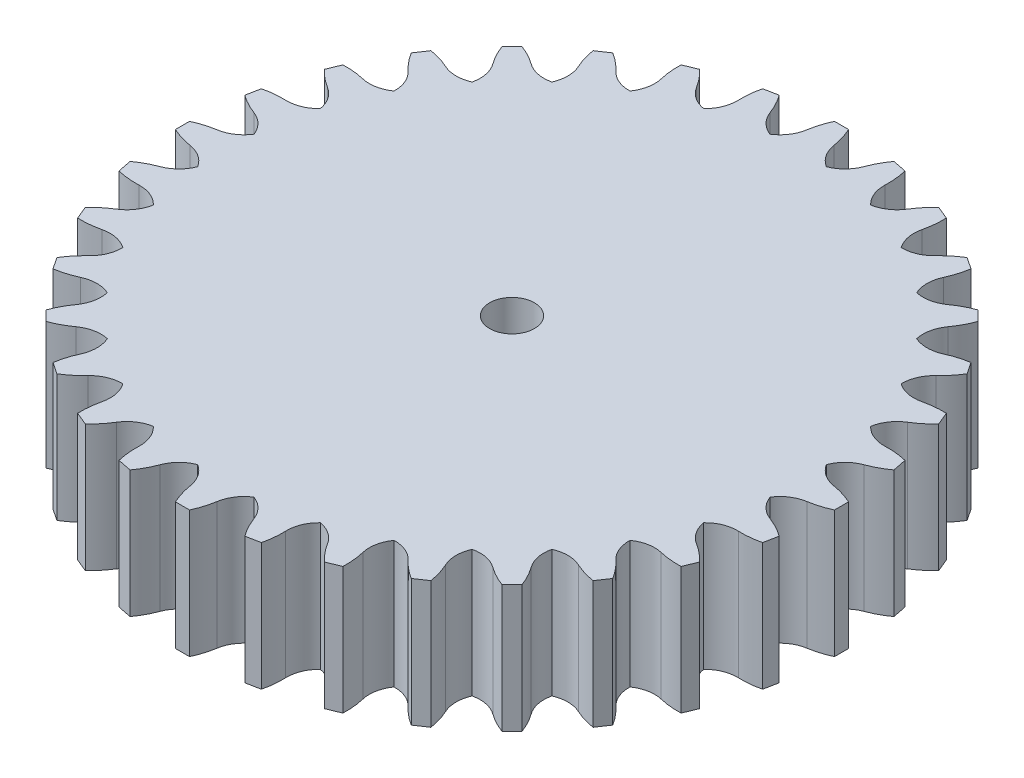
SolidWorks part; units mm, degrees
ref_plane "Front Plane" through (0, 0, 0) normal (0, 0, 1) x (1, 0, 0)
ref_plane "Top Plane" through (0, 0, 0) normal (0, 1, 0) x (1, 0, 0)
ref_plane "Right Plane" through (0, 0, 0) normal (1, 0, 0) x (0, 0, -1)
sketch "Sketch1" plane through (0, 0, 0) normal (0, 1, 0) x (1, 0, 0)
  line L2 (0.5, 23.3473) -> (-0.5, 23.3473)
  line L3 (-1, 20.3473) -> (1, 20.3473)
  line L4 (0, 23.3473) -> (0, 20.3473)
  line L6 (0, -1.5875) -> (0, 1.5875)
  line L7 (-0.7246, -1.4125) -> (0.7246, -1.4125)
  line L8 (0, 21.8473) -> (0.9583, 21.8473)
  line L9 (0, 21.8473) -> (-0.9583, 21.8473)
  line L10 (-2, 20.2734) -> (2, 20.2734)
  circle A0 centre (0, 0) radius 20.3718
  arc A1 (-1, 20.3473) -> (-0.5, 23.3473) centre (4.6965, 20.9395) cw
  arc A2 (0.5, 23.3473) -> (1, 20.3473) centre (-4.6965, 20.9395) cw
  circle A3 centre (0, 0) radius 1.5875
  arc A4 (-0.9583, 21.8473) -> (-2, 20.2734) centre (-3.2156, 22.2096) cw
  arc A5 (0.9583, 21.8473) -> (2, 20.2734) centre (3.2156, 22.2096) ccw
  dimension "D4" = 5.7272
  dimension "D5" = 40.7437
  dimension "D6" = 3.175
  dimension "D2" = 2
  dimension "D3" = 1
  dimension "D7" = 0.175
  dimension "D8" = 4
extrude "Boss-Extrude1" add sketch "Sketch1" along normal blind 9 contours A1 L2 A2 L3 | L10 A5 L8 L9 A4
sketch "Sketch4" plane through (0, 0, 0) normal (1, 0, 0) x (0, 0, -1)
  line L0 (0, 0) -> (0, 7.6311)
pattern_circular "CirPattern2" count 32 over 360 about axis through (0, 0, 0) along (0, 1, 0) of "Boss-Extrude1" reverse direction yes
extrude "Boss-Extrude3" add sketch "Sketch1<5>" along normal blind 9 contours L10 A0 A3 region at (14.6692, 0, -13.2932)
sketch "Sketch1<5>" plane through (0, 0, 0) normal (0, 1, 0) x (1, 0, 0) same geometry as "Sketch1"
equation "\"teeth\"= 32'num of teeth in gear"
equation "\"gearRadius\"= \"teeth\" * 4 / ( 2 * Pi )"
equation "\"D5@Sketch1\"=\"gearRadius\"*2"
equation "\"D1@CirPattern2\"=\"teeth\""
